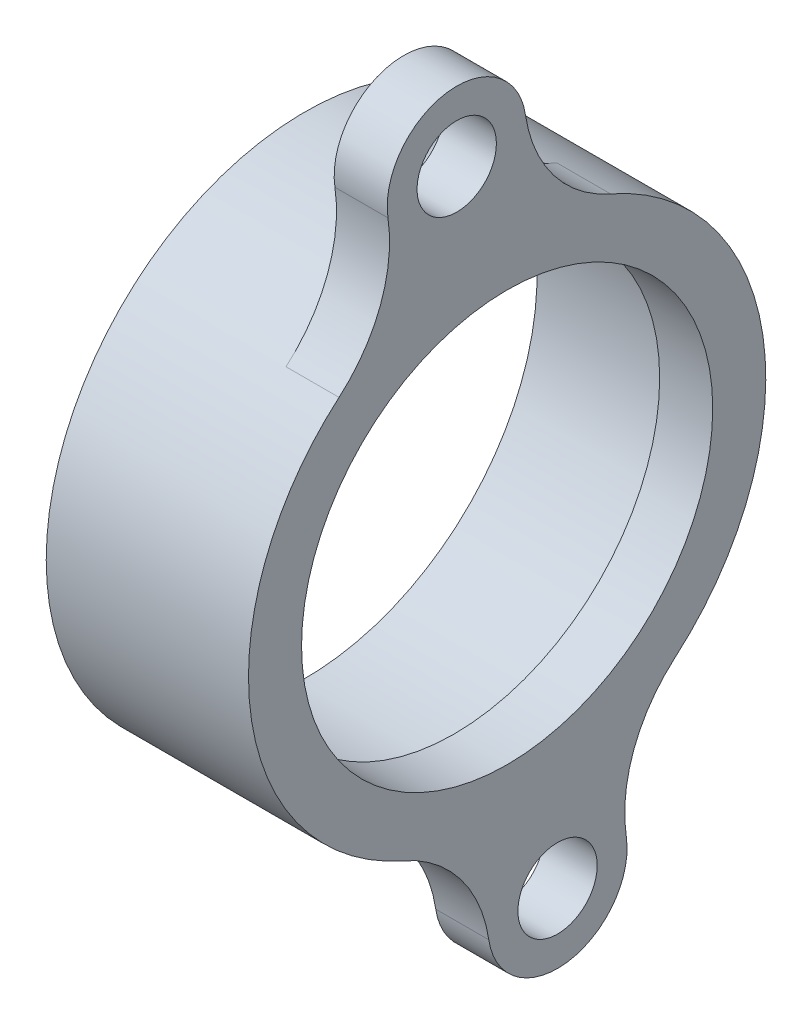
SolidWorks part; units mm, degrees
ref_plane "Front Plane" through (0, 0, 0) normal (0, 0, 1) x (1, 0, 0)
ref_plane "Top Plane" through (0, 0, 0) normal (0, 1, 0) x (1, 0, 0)
ref_plane "Right Plane" through (0, 0, 0) normal (1, 0, 0) x (0, 0, -1)
sketch "Sketch1" plane through (0, 0, 0) normal (0, 0, 1) x (1, 0, 0)
  line L0 (24.6062, 12.3825) -> (31.75, 12.3825)
  line L1 (31.75, 12.3825) -> (31.75, 11.1125)
  line L2 (31.75, 11.1125) -> (24.6062, 11.1125)
  line L4 (24.6062, 11.1125) -> (24.6062, 12.3825)
  line L5 (0, 0) -> (40.0174, 0) construction
  dimension "D1" = 1.27
  dimension "D2" = 7.1437
revolve "Revolve1" add sketch "Sketch1" angle 360 about L5
sketch "Sketch2" plane through (31.75, 0, 0) normal (1, 0, 0) x (0, 0, -1)
  line L0 (3.6094, -24.1842) -> (-3.6094, 24.1842) construction
  line L1 (-5.7046, 15.681) -> (0.8773, 16.6633) construction
  line L2 (-27.3391, -4.0802) -> (27.3391, 4.0802) construction
  line L4 (-4.094, 11.9086) -> (0.4385, 12.5851) construction
  line L5 (0.4385, 12.5851) -> (2.1189, 16.8486) construction
  line L6 (2.1189, 16.8486) -> (-0.7332, 20.4356) construction
  line L7 (-0.7332, 20.4356) -> (-5.2657, 19.7592) construction
  line L8 (-5.2657, 19.7592) -> (-6.9461, 15.4957) construction
  line L9 (-6.9461, 15.4957) -> (-4.094, 11.9086) construction
  arc A0 (-8.0474, 9.4109) -> (-4.9489, -11.3505) centre (0, 0) ccw
  circle A1 centre (0, 0) radius 12.3825 construction
  arc A7 (0.8773, 16.6633) -> (-5.7046, 15.681) centre (-2.4136, 16.1721) ccw
  arc A8 (-8.0474, 9.4109) -> (-5.7046, 15.681) centre (-12.5371, 14.6613) ccw
  arc A9 (0.8773, 16.6633) -> (4.9489, 11.3505) centre (7.7099, 17.683) ccw
  circle A10 centre (0, 0) radius 9.8425
  circle A11 centre (0, 0) radius 11.1125 construction
  arc A12 (5.7046, -15.681) -> (8.0474, -9.4109) centre (12.5371, -14.6613) cw
  arc A14 (5.7046, -15.681) -> (-0.8773, -16.6633) centre (2.4136, -16.1721) cw
  arc A15 (-4.9489, -11.3505) -> (-0.8773, -16.6633) centre (-7.7099, -17.683) cw
  arc A16 (8.0474, -9.4109) -> (4.9489, 11.3505) centre (0, 0) ccw
  circle A17 centre (-2.4136, 16.1721) radius 3.9688 construction
  arc A18 (0.9017, 20.8448) -> (-6.9488, 19.6731) centre (-3.0235, 20.259) ccw construction
  arc A19 (-0.9017, -20.8448) -> (6.9488, -19.6731) centre (3.0235, -20.259) ccw construction
  point P6 (3.6094, -24.1842)
  point P8 (-3.6094, 24.1842)
  point P12 (0, 0)
  point P31 (0, 0)
  dimension "D1" = 1.27
  dimension "D2" = 3.3274
  dimension "D3" = 7.9375
extrude "Boss-Extrude1" add sketch "Sketch2" along normal blind 2.54
hole_wizard "#6 Clearance Hole1" positions "Sketch3" profile "Sketch5" hole size "#6" standard "ANSI Inch" end condition up to next
sketch "Sketch3" plane through (34.29, 0, 0) normal (1, 0, 0) x (0, 0, -1)
  point P0 (-2.4136, 16.1721)
  point P3 (2.4136, -16.1721)
sketch "Sketch5" plane through (34.29, 16.1721, 2.4136) normal (0, 1, 0) x (0, 0, -1)
  line L0 (0, 0) -> (0, 2.54)
  line L1 (0, 2.54) -> (1.8986, 2.54)
  line L2 (1.8986, 2.54) -> (1.8986, 0)
  line L5 (1.8986, 0) -> (0, 0)
  line L11 (0, -6.35) -> (0, 107.95) construction
  dimension "Thru Hole Dia." = 3.7973
  dimension "Thru Hole Depth" = 2.54
